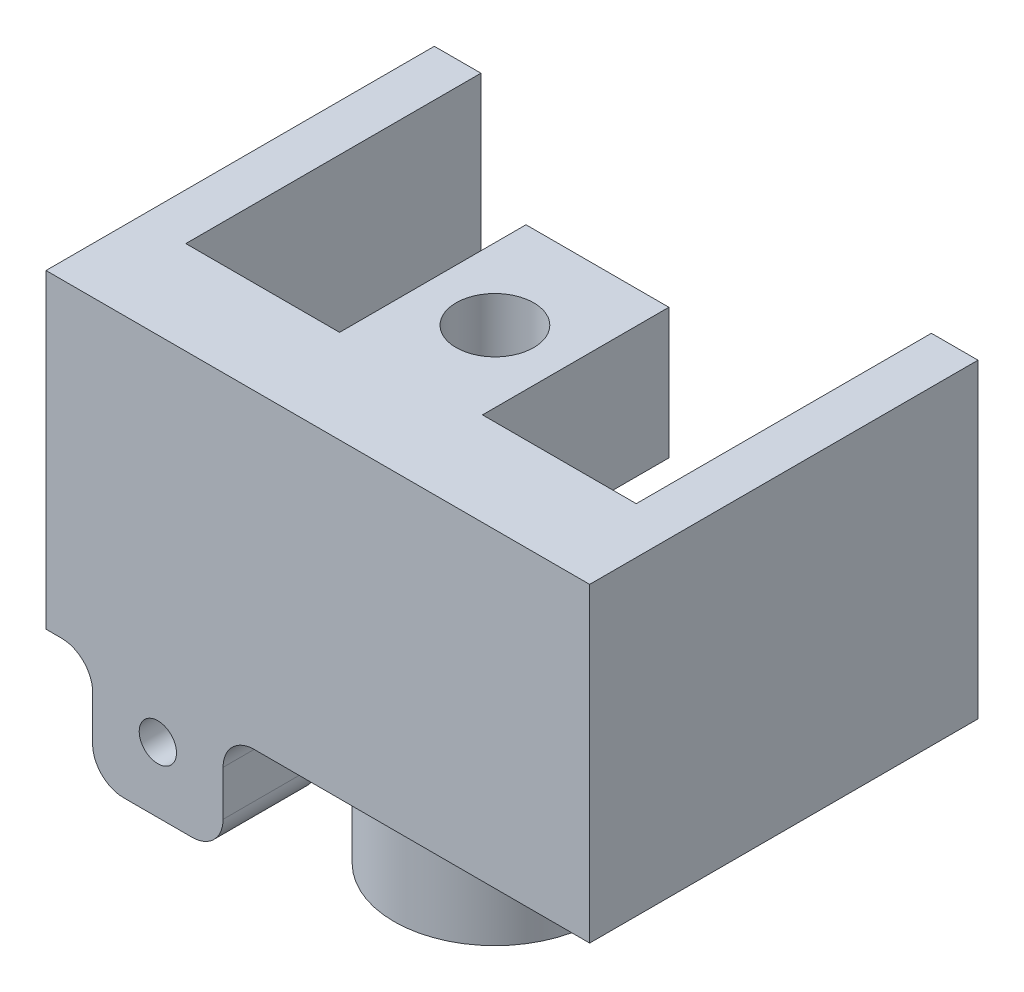
SolidWorks part; units mm, degrees
ref_plane "Front Plane" through (0, 0, 0) normal (0, 0, 1) x (1, 0, 0)
ref_plane "Top Plane" through (0, 0, 0) normal (0, 1, 0) x (1, 0, 0)
ref_plane "Right Plane" through (0, 0, 0) normal (1, 0, 0) x (0, 0, -1)
sketch "Sketch1" plane through (0, 0, 0) normal (0, 1, 0) x (1, 0, 0)
  line L0 (-7.25, 6.8) -> (-7.25, -2.7)
  line L1 (-7.25, -2.7) -> (-2.3, -2.7)
  line L2 (-2.3, -2.7) -> (-2.3, 3.3)
  line L3 (-2.3, 3.3) -> (2.3, 3.3)
  line L4 (2.3, 3.3) -> (2.3, -2.7)
  line L5 (2.3, -2.7) -> (7.25, -2.7)
  line L6 (7.25, -2.7) -> (7.25, 6.8)
  line L7 (7.25, 6.8) -> (8.75, 6.8)
  line L8 (8.75, 6.8) -> (8.75, -5.7)
  line L9 (8.75, -5.7) -> (-8.75, -5.7)
  line L10 (-8.75, -5.7) -> (-8.75, 6.8)
  line L11 (-8.75, 6.8) -> (-7.25, 6.8)
  circle A0 centre (0, 0) radius 1.25
  point P11 (0, 3.3)
  dimension "D7" = 2.5
  dimension "D1" = 4.6
  dimension "D2" = 6
  dimension "D3" = 9.5
  dimension "D4" = 3
  dimension "D5" = 1.5
  dimension "D6" = 14.5
  dimension "D8" = 3.3
extrude "Boss-Extrude1" add sketch "Sketch1" along normal mid plane 10
sketch "Sketch4" plane through (2.3, 0, 0) normal (1, 0, 0) x (0, 0, -1)
  line L0 (3.3, 0.8) -> (-1.25, 0.8)
  line L1 (3.3, 5) -> (3.3, -5) construction
  line L2 (-1.25, 0.8) -> (-1.25, 0.45)
  line L3 (-1.25, 0.45) -> (3.3, -4.1)
  line L4 (3.3, -4.1) -> (3.3, 0.8)
  line L5 (-1.25, -5) -> (1.25, -5) construction
  line L6 (-1.25, -5) -> (1.25, -5) construction
  line L8 (0, -0.8) -> (0, 0.8) construction
  point P7 (0, -5)
  point P8 (0, 0)
  point P13 (0, 0)
  point P14 (2.5, -2.3994)
  dimension "D1" = 45
  dimension "D2" = 1.6
extrude "Cut-Extrude3" cut sketch "Sketch4" against normal up to surface (4.6 mm away) up to face at (-2.3, 0, -0.3)
sketch "Sketch5" plane through (0, -5, 0) normal (0, -1, 0) x (1, 0, 0)
  circle A1 centre (0, 0) radius 2.25
  circle A2 centre (0, 0) radius 3.25
  dimension "D1" = 4.5
  dimension "D2" = 1
extrude "Boss-Extrude2" add sketch "Sketch5" along normal blind 5
fillet "Fillet1" radius 1 2 edges at (3.25, -5, 0) (-3.25, -5, 0)
fillet "Fillet2" radius 1 2 edges at (0, -5, -3.25) (0, -5, 3.25)
sketch "Sketch6" plane through (0, -5, 0) normal (0, -1, 0) x (1, 0, 0)
  line L0 (-8.75, 5.7) -> (8.75, 5.7) construction
  line L1 (-7.25, 2.7) -> (-3.05, 2.7)
  line L2 (-7.25, 2.7) -> (-7.25, 5.7)
  line L3 (-7.25, 5.7) -> (-3.05, 5.7)
  line L4 (-3.05, 2.7) -> (-3.05, 5.7)
  point P7 (0, 0)
  dimension "D1" = 4.2
extrude "Boss-Extrude3" add sketch "Sketch6" along normal blind 3.45
sketch "Sketch7" plane through (0, 0, 2.7) normal (0, 0, -1) x (-1, 0, 0)
  line L0 (7.25, -8.45) -> (3.05, -8.45) construction
  line L1 (8.75, 5) -> (8.75, -5) construction
  circle A0 centre (5.15, -6.35) radius 0.6
  dimension "D1" = 1.2
  dimension "D2" = 2.1
  dimension "D3" = 3.6
extrude "Cut-Extrude4" cut sketch "Sketch7" against normal through all
fillet "Fillet3" radius 1 4 edges at (-3.05, -5, 4.3299) (-3.05, -8.45, 4.2) (-7.25, -8.45, 4.2) (-7.25, -5, 4.2)
